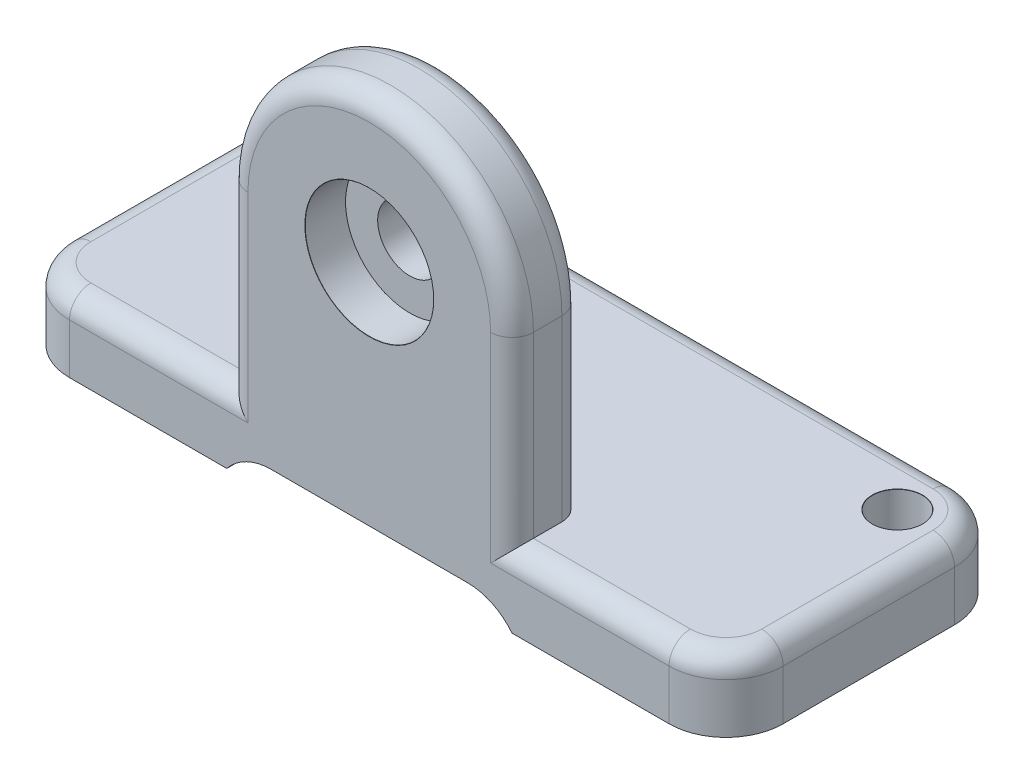
SolidWorks part; units mm, degrees
ref_plane "Plano frontal" through (0, 0, 0) normal (0, 0, 1) x (1, 0, 0)
ref_plane "Plano superior" through (0, 0, 0) normal (0, 1, 0) x (1, 0, 0)
ref_plane "Plano direito" through (0, 0, 0) normal (1, 0, 0) x (0, 0, -1)
sketch "Esboço1" plane through (0, 0, 0) normal (0, 1, 0) x (1, 0, 0)
  line L1 (0, 0) -> (100, 0)
  line L2 (0, 0) -> (0, 40)
  line L3 (0, 40) -> (100, 40)
  line L4 (100, 0) -> (100, 40)
  dimension "D1" = 40
  dimension "D2" = 100
extrude "Ressalto-extrusão1" add sketch "Esboço1" along normal blind 10
sketch "Esboço2" plane through (0, 0, 0) normal (0, 0, 1) x (1, 0, 0)
  line L0 (30, 0) -> (30, 35)
  line L1 (0, 0) -> (100, 0) construction
  line L2 (70, 0) -> (70, 35)
  line L3 (30, 0) -> (70, 0)
  arc A0 (30, 35) -> (70, 35) centre (50, 35) cw
  dimension "D3" = 20
  dimension "D1" = 35
  dimension "D2" = 50
extrude "Ressalto-extrusão2" add sketch "Esboço2" against normal blind 10
sketch "Esboço3" plane through (0, 0, 0) normal (0, 0, 1) x (1, 0, 0)
  line L5 (0, 0) -> (100, 0) construction
  line L6 (30.0375, 0) -> (70, 0)
  line L7 (30.0375, 0) -> (30.0375, 3)
  line L8 (30.0375, 3) -> (70, 3)
  line L9 (70, 0) -> (70, 3)
  line L10 (70, 10) -> (70, 35) construction
  dimension "D1" = 3
extrude "Corte-extrusão1" cut sketch "Esboço3" against normal through all
fillet "Filete1" radius 8 6 edges at (100, 5, 0) (100, 5, -40) (0, 5, -40) (0, 5, 0) (70, 3, -20) (30.0375, 3, -20)
hole_wizard "Furo de diâmetro Ø7.0 (7)1" positions "Esboço7" profile "Esboço8" hole size "Ø7.0" standard "Ansi Metric" end condition through all
sketch "Esboço7" plane through (0, 10, 0) normal (0, 1, 0) x (1, 0, 0)
  point P0 (8, 32)
sketch "Esboço8" plane through (8, 10, -32) normal (1, 0, 0) x (0, 0, 1)
  line L0 (0, 0) -> (0, 10)
  line L1 (0, 10) -> (3.5, 10)
  line L2 (3.5, 10) -> (3.5, 0.025)
  line L3 (3.5, 0.025) -> (3.525, 0)
  line L5 (3.525, 0) -> (0, 0)
  line L6 (-3.5, 0.025) -> (-3.525, 0) construction
  line L11 (0, -6.35) -> (0, 107.95) construction
  dimension "Thru Hole Dia." = 7
  dimension "Thru Hole Depth" = 10
  dimension "Near C'Sink Dia." = 7.05
  dimension "Near C'Sink Angle" = 90
hole_wizard "Furo de diâmetro Ø7.0 (7)3" positions "Esboço11" profile "Esboço12" hole size "Ø7.0" standard "Ansi Metric" end condition through all
sketch "Esboço11" plane through (0, 10, 0) normal (0, 1, 0) x (1, 0, 0)
  point P0 (92, 32)
sketch "Esboço12" plane through (92, 10, -32) normal (1, 0, 0) x (0, 0, 1)
  line L0 (0, 0) -> (0, 10)
  line L1 (0, 10) -> (3.5, 10)
  line L2 (3.5, 10) -> (3.5, 0.025)
  line L3 (3.5, 0.025) -> (3.525, 0)
  line L5 (3.525, 0) -> (0, 0)
  line L6 (-3.5, 0.025) -> (-3.525, 0) construction
  line L11 (0, -6.35) -> (0, 107.95) construction
  dimension "Thru Hole Dia." = 7
  dimension "Thru Hole Depth" = 10
  dimension "Near C'Sink Dia." = 7.05
  dimension "Near C'Sink Angle" = 90
hole_wizard "Rebaixo para parafuso de cabeça sextavada de M81" positions "Esboço15" profile "Esboço16" counterbore size "M8" standard "Ansi Metric" end condition through all
sketch "Esboço15" plane through (0, 0, 0) normal (0, 0, 1) x (1, 0, 0)
  point P0 (50, 35)
sketch "Esboço16" plane through (50, 35, 0) normal (1, 0, 0) x (0, -1, 0)
  line L0 (0, 0) -> (0, 40)
  line L1 (0, 40) -> (4.5, 40)
  line L3 (4.5, 40) -> (4.5, 5.68)
  line L4 (9.005, 5.68) -> (4.5, 5.68)
  line L5 (9.005, 5.68) -> (9.005, 0.025)
  line L6 (9.005, 0.025) -> (9.03, 0)
  line L7 (9.03, 0) -> (0, 0)
  line L8 (-9.005, 0.025) -> (-9.03, 0) construction
  line L11 (0, -6.35) -> (0, 107.95) construction
  dimension "Thru Hole Dia." = 9
  dimension "Thru Hole Depth" = 40
  dimension "C'Bore Dia." = 18.01
  dimension "C'Bore Depth" = 5.68
  dimension "Near C'Sink Dia." = 18.06
  dimension "Near C'Sink Angle" = 90
fillet "Filete3" radius 3 15 edges at (70, 22.5, 0) (30, 22.5, 0) (70, 22.5, -10) (30, 22.5, -10) (50, 55, 0) (50, 55, -10) (19, 10, 0) (2.3431, 10, -2.3431) (0, 10, -20) (2.3431, 10, -37.6569) (50, 10, -40) (97.6569, 10, -37.6569) (100, 10, -20) (97.6569, 10, -2.3431) (81, 10, 0)
